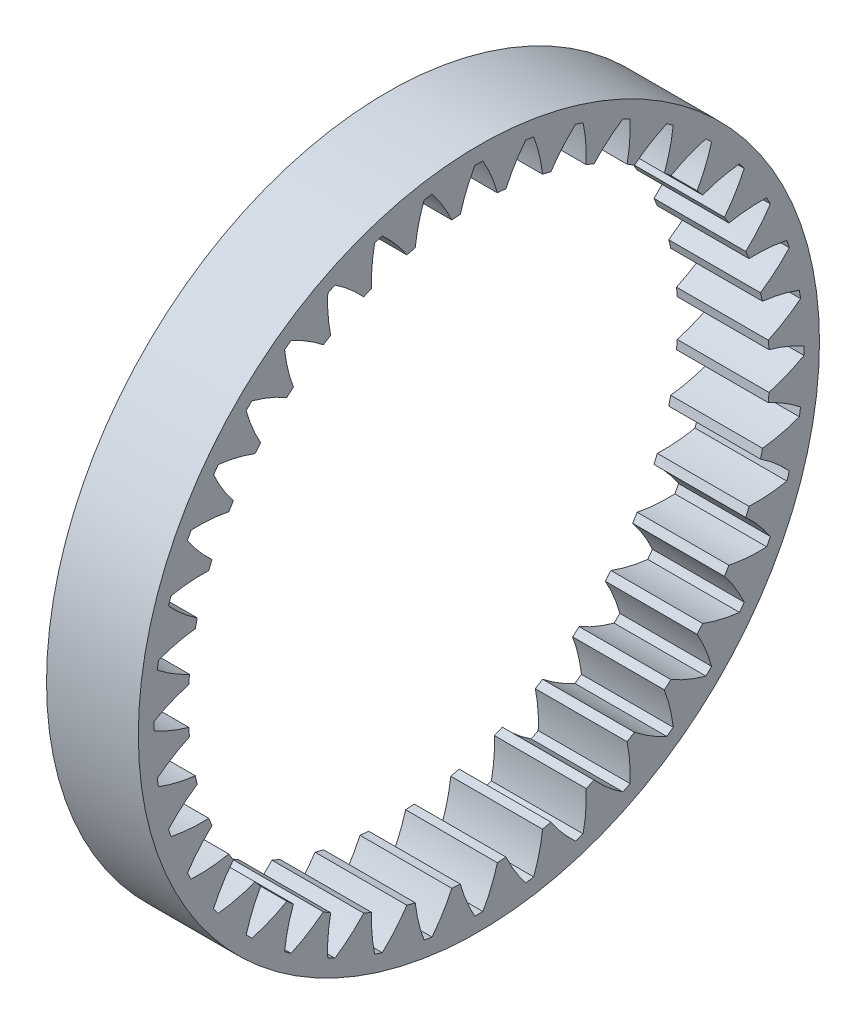
SolidWorks part; units mm, degrees
ref_plane "Plane1" through (0, 0, 0) normal (0, 0, 1) x (1, 0, 0)
ref_plane "Plane2" through (0, 0, 0) normal (0, 1, 0) x (1, 0, 0)
ref_plane "Plane3" through (0, 0, 0) normal (1, 0, 0) x (0, 0, -1)
sketch "HoldingSke" plane through (0, 0, 0) normal (0, 1, 0) x (1, 0, 0)
  line L0 (0, 0) -> (0.383, -0.3214)
  line L1 (-15, 0) -> (100, 0) construction
  line L2 (0, 0) -> (-2.1039, 2.3779)
  line L3 (0, 0) -> (-11.863, 4.5341)
  line L4 (0, 0) -> (6.6156, 5.5511)
  line L5 (0, 0) -> (-23.7986, -8.8762)
  line L6 (0, 0) -> (-10.5278, -7.1032)
  line L7 (-2.1039, 2.3779) -> (3.3635, 27.1825)
  line L8 (-76.2, 4.3779) -> (-54.61, 4.3779)
  line L9 (-71.009, 38.7566) -> (-53.1078, 45.2721)
  line L10 (-76.2, 71.12) -> (104.1128, 71.12)
  line L11 (0, 0) -> (-12, 0)
  line L12 (-76.2, 101.6) -> (-76.133, 101.6)
  line L13 (24.9733, 27.94) -> (52.9518, 28.4284)
  line L14 (24.9733, 27.94) -> (24.9743, 27.94)
  line L15 (24.9733, 27.94) -> (100.4006, 29.5858)
  circle A0 centre (0, 0) radius 12.5
  circle A1 centre (0, 0) radius 12.7
  circle A2 centre (0, 0) radius 12.7
  dimension "MHD" = 25.4
  dimension "Hub_dia" = 25.4
  dimension "Diameter" = 25
  dimension "Num_teeth" = 40
  dimension "Pitch" = 0.5
  dimension "Overall_len" = 25.4
  dimension "Show_teeth" = 40
  dimension "Thickness" = 12.7
  dimension "OAL" = 25.4001
  dimension "T_dim" = 21.59
  dimension "Ap" = 20
  dimension "H" = 19.05
  dimension "Pitch_radius" = 180.3128
  dimension "Width" = 12
  dimension "Backlash" = 0.067
  dimension "Addendum_fac" = 1
  dimension "Dedendum_fac" = 1.25
  dimension "Clearance_fac" = 0.25
  dimension "Dedendum_add" = 0.001
  dimension "Module" = 2
sketch "BasProSke" plane through (0, 0, 0) normal (0, 1, 0) x (1, 0, 0)
  line L0 (-10, 0) -> (60, 0) construction
  line L1 (0, 38) -> (0, 42.5264)
  line L2 (0, 38) -> (12, 38)
  line L3 (12, 38) -> (12, 42.5264)
  line L4 (12, 42.5264) -> (0, 42.5264)
  dimension "Thickness" = 12
  dimension "Diameter" = 85.0528
  dimension "Inside_diameter" = 76
revolve "Base-Revolve" add sketch "BasProSke" angle 360 about L0
sketch "TooCutSke" plane through (0, 0, 0) normal (1, 0, 0) x (0, 0, -1)
  line L3 (1.7379, 39.9622) -> (1.7379, 53.6633) construction
  line L4 (0, 0) -> (0, 59.563) construction
  line L5 (0, 0) -> (-5.3609, 68.1169) construction
  line L6 (-16.8604, 32.6066) -> (35.072, 36.6938) construction
  circle A0 centre (0, 0) radius 40 construction
  circle A1 centre (0, 0) radius 42.501 construction
  circle A2 centre (0, 0) radius 33.8289 construction
  circle A3 centre (0, 0) radius 37.9746 construction
  arc A4 (2.4273, 37.8969) -> (0.5225, 42.4978) centre (-16.8604, 32.6066) ccw
  arc A5 (2.4273, 37.8969) -> (-2.4273, 37.8969) centre (0, 0) ccw
  arc A6 (0.5225, 42.4978) -> (-0.5225, 42.4978) centre (0, 0) ccw
  arc A7 (-0.5225, 42.4978) -> (-2.4273, 37.8969) centre (16.8604, 32.6066) ccw
  dimension "Pitch_dia" = 80
  dimension "Base_dia" = 67.6579
  dimension "Root_dia" = 85.002
  dimension "Overcut_dia" = 75.9492
  dimension "Flank_rad" = 20
  dimension "Half_ang" = 4.5
  dimension "Half_CT" = 1.7379
extrude "ToothCut" cut sketch "TooCutSke" along normal through all
fillet "Breaks" [suppressed] radius 0.2
fillet "RootFillets" [suppressed] radius 0.501
pattern_circular "TeethCuts" count 40 every 9 about axis through (-10, 0, 0) along (1, 0, 0) of "RootFillets", "Breaks", "ToothCut"
sketch "Sketch1" [suppressed] plane through (0, 0, 0) normal (1, 0, 0) x (0, 0, -1)
  circle A0 centre (0, 0) radius 42.501
extrude "Extrude-Thin1" [suppressed] add sketch "Sketch1" along normal through all thin thin type one direction wall 2
sketch "Sketch2" plane through (0, 0, 0) normal (1, 0, 0) x (0, 0, -1)
  circle A0 centre (0, 0) radius 42.5264
extrude "Extrude-Thin3" add sketch "Sketch2" along normal through all thin thin type one direction wall 2
equation "' \"Module@HoldingSke\" = 6.35"
equation "' \"Num_teeth@HoldingSke\" = 24"
equation "' \"Ap@HoldingSke\" =  14.5"
equation "' \"Ap@HoldingSke\" = 14.5"
equation "' \"Width@HoldingSke\" = 12"
equation "' \"Diameter@HoldingSke\" = 8 * 25.4"
equation "' \"Show_teeth@HoldingSke\" = 100"
equation "' \"Backlash@HoldingSke\" = 0.009 * 25.4"
equation "' \"Addendum_fac@HoldingSke\" = 1.0"
equation "' \"Dedendum_fac@HoldingSke\" = 1.25"
equation "' \"Dedendum_add@HoldingSke\" = 0.00005 * 25.4"
equation "' \"Clearance_fac@HoldingSke\" = 0.25"
equation "\"Pitch@HoldingSke\" = 1 / \"Module@HoldingSke\" "
equation "\"Overcut_dia@TooCutSke\" = (\"Num_teeth@HoldingSke\" - 2 * \"Addendum_fac@HoldingSke\") / \"Pitch@HoldingSke\" - 0.002 * 25.4"
equation "\"Pitch_dia@TooCutSke\" = \"Num_teeth@HoldingSke\" / \"Pitch@HoldingSke\""
equation "\"Base_dia@TooCutSke\" = \"Num_teeth@HoldingSke\" / \"Pitch@HoldingSke\" * cos((\"Ap@HoldingSke\"  * 3.14159265 / 180)) * 0.90"
equation "\"Root_dia@TooCutSke\" = \"Num_teeth@HoldingSke\"  / \"Pitch@HoldingSke\" + 2 *  \"Dedendum_fac@HoldingSke\"/ \"Pitch@HoldingSke\" + \"Dedendum_add@HoldingSke\" * 2"
equation "\"Half_ang@TooCutSke\" = 180 / \"Num_teeth@HoldingSke\""
equation "\"Half_CT@TooCutSke\" = \"Num_teeth@HoldingSke\" / \"Pitch@HoldingSke\" * sin((3.14159265 / 2 / \"Num_teeth@HoldingSke\")) / 2 + 10 * \"Backlash@HoldingSke\" / 4"
equation "\"Flank_rad@TooCutSke\" = \"Num_teeth@HoldingSke\" / \"Pitch@HoldingSke\" / 4"
equation "\"Radius@RootFillets\"= \"Clearance_fac@HoldingSke\" / \"Pitch@HoldingSke\" + \"Dedendum_add@HoldingSke\""
equation "\"Break_rad@Breaks\" = 0.02 / \"Pitch@HoldingSke\" * 5"
equation "\"Num_teeth@TeethCuts\" = int( \"Show_teeth@HoldingSke\" ) + 1"
equation "\"Num_teeth@TeethCuts\" = ((sgn( \"Num_teeth@TeethCuts\" - \"Num_teeth@HoldingSke\" )-1)*( \"Num_teeth@TeethCuts\" - \"Num_teeth@HoldingSke\" ))/-2+ \"Num_teeth@HoldingSke\""
equation "\"Num_teeth@TeethCuts\" = ((sgn( \"Num_teeth@TeethCuts\" - 2.0)+1)*( \"Num_teeth@TeethCuts\" - 2.0))/2 +2.0"
equation "\"Angle@TeethCuts\" = 360.0 / \"Num_teeth@HoldingSke\""
equation "\"Diameter@BasProSke\" = \"Num_teeth@HoldingSke\"  / \"Pitch@HoldingSke\" + 2 *  \"Dedendum_fac@HoldingSke\"/ \"Pitch@HoldingSke\" + \"Dedendum_add@HoldingSke\" * 2 + 0.002 * 25.4"
equation "\"Diameter@BasProSke\" = ((sgn( \"Diameter@BasProSke\"  - \"Diameter@HoldingSke\" )+1)*( \"Diameter@BasProSke\"  - \"Diameter@HoldingSke\" ))/2 + \"Diameter@HoldingSke\""
equation "\"Inside_diameter@BasProSke\" =  (\"Num_teeth@HoldingSke\" - 2 * \"Addendum_fac@HoldingSke\") / \"Pitch@HoldingSke\" "
equation "\"Thickness@BasProSke\"  = \"Width@HoldingSke\""
